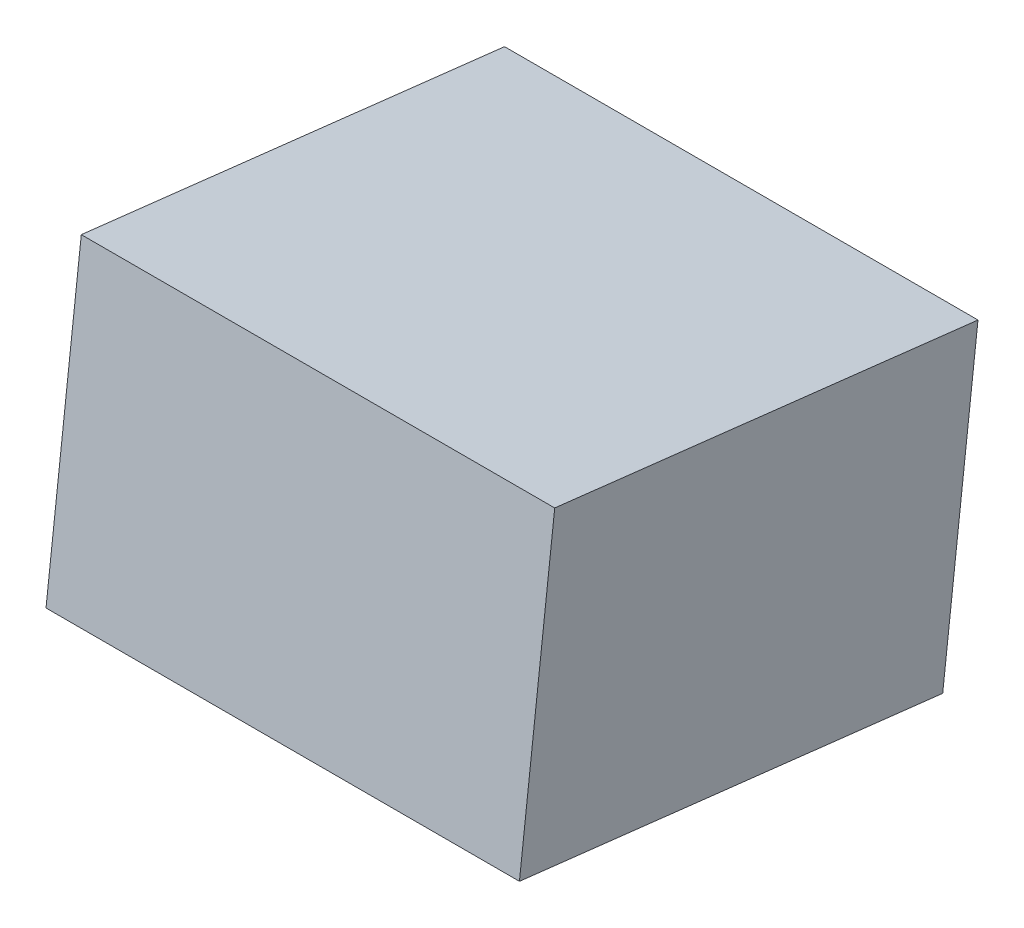
SolidWorks part; units mm, degrees
ref_plane "Front Plane" through (0, 0, 0) normal (0, 0, 1) x (1, 0, 0)
ref_plane "Top Plane" through (0, 0, 0) normal (0, 1, 0) x (1, 0, 0)
ref_plane "Right Plane" through (0, 0, 0) normal (1, 0, 0) x (0, 0, -1)
sketch "Sketch1" plane through (0, 358.8799, -41.4225) normal (0, 0.9934, -0.1147) x (1, 0, 0)
  line L1 (-235, 60.2443) -> (-35, 60.2443)
  line L2 (-235, 60.2443) -> (-235, 240.2443)
  line L3 (-235, 240.2443) -> (-35, 240.2443)
  line L4 (-35, 60.2443) -> (-35, 240.2443)
  line L5 (-235, 60.2443) -> (-35, 240.2443) construction
  line L6 (-235, 240.2443) -> (-35, 60.2443) construction
  point P0 (-135, 150.2443)
  dimension "D1" = 180
  dimension "D2" = 200
extrude "Boss-Extrude1" add sketch "Sketch1" along normal blind 130
